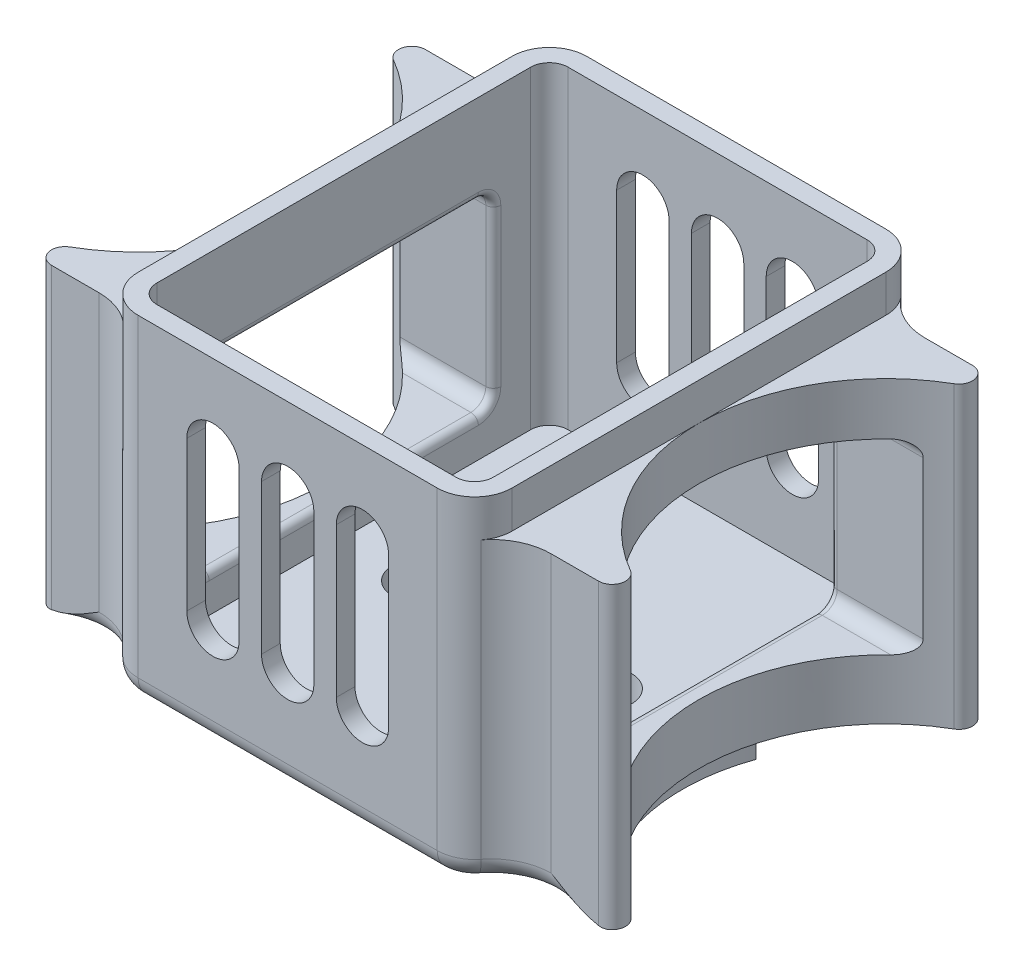
SolidWorks part; units mm, degrees
ref_plane "Alzado" through (0, 0, 0) normal (0, 0, 1) x (1, 0, 0)
ref_plane "Planta" through (0, 0, 0) normal (0, 1, 0) x (1, 0, 0)
ref_plane "Vista lateral" through (0, 0, 0) normal (1, 0, 0) x (0, 0, -1)
sketch "Croquis1" plane through (0, 0, 0) normal (0, 1, 0) x (1, 0, 0)
  line L0 (-25, 0) -> (-50, 0) construction
  line L1 (20, -30) -> (-20, -30)
  line L2 (25, -25) -> (25, 25)
  line L3 (20, 30) -> (-20, 30)
  line L4 (-25, -25) -> (-25, 25)
  line L5 (25, -30) -> (-25, 30) construction
  line L6 (25, 30) -> (-25, -30) construction
  line L7 (-50, 25) -> (-25, 25)
  line L8 (-50, -25) -> (-25, -25)
  line L9 (25, 25) -> (50, 25)
  line L10 (25, -25) -> (50, -25)
  arc A0 (20, -30) -> (25, -25) centre (20, -25) ccw
  arc A1 (-25, -25) -> (-20, -30) centre (-20, -25) ccw
  arc A2 (25, 25) -> (20, 30) centre (20, 25) ccw
  arc A3 (-20, 30) -> (-25, 25) centre (-20, 25) ccw
  arc A4 (-50, -25) -> (-50, 25) centre (-50, 0) ccw
  arc A5 (50, 25) -> (50, -25) centre (50, 0) ccw
  point P0 (0, 0)
  dimension "D3" = 5
  dimension "D4" = 5
  dimension "D5" = 5
  dimension "D6" = 5
  dimension "D8" = 25
  dimension "D1" = 50
  dimension "D2" = 60
  dimension "D7" = 25
extrude "Saliente-Extruir1" add sketch "Croquis1" along normal blind 45 contours L3 A3 L4 A1 L1 A0 L2 A2 | A4 L4 L7 | A4 L8 L4 | A5 L2 L10 | A5 L9 L2
sketch "Croquis2" plane through (0, 45, 0) normal (0, 1, 0) x (1, 0, 0)
  line L0 (-25, 25) -> (-25, -25)
  line L1 (25, 25) -> (25, -25)
  line L2 (20, 27.5) -> (-20, 27.5)
  line L3 (-22.5, 25) -> (-22.5, -25)
  line L4 (-20, -27.5) -> (20, -27.5)
  line L5 (22.5, 25) -> (22.5, -25)
  line L6 (20, 30) -> (-20, 30)
  line L7 (-25, 25) -> (-50, 25)
  line L8 (-50, -25) -> (-25, -25)
  line L9 (-20, -30) -> (20, -30)
  line L10 (25, -25) -> (50, -25)
  line L11 (50, 25) -> (25, 25)
  line L12 (20, 30) -> (-20, 30)
  line L15 (-20, -30) -> (20, -30)
  arc A0 (-20, 27.5) -> (-22.5, 25) centre (-20, 25) ccw
  arc A1 (-22.5, -25) -> (-20, -27.5) centre (-20, -25) ccw
  arc A2 (20, -27.5) -> (22.5, -25) centre (20, -25) ccw
  arc A3 (22.5, 25) -> (20, 27.5) centre (20, 25) ccw
  arc A6 (-20, 30) -> (-25, 25) centre (-20, 25) ccw
  arc A7 (-50, -25) -> (-50, 25) centre (-50, 0) ccw
  arc A8 (-25, -25) -> (-20, -30) centre (-20, -25) ccw
  arc A9 (20, -30) -> (25, -25) centre (20, -25) ccw
  arc A10 (50, 25) -> (50, -25) centre (50, 0) ccw
  arc A11 (25, 25) -> (20, 30) centre (20, 25) ccw
  arc A12 (-20, 30) -> (-25, 25) centre (-20, 25) ccw
  arc A14 (-25, -25) -> (-20, -30) centre (-20, -25) ccw
  arc A15 (20, -30) -> (25, -25) centre (20, -25) ccw
  arc A17 (25, 25) -> (20, 30) centre (20, 25) ccw
  dimension "D1" = 0
  dimension "D2" = 2.5
extrude "Cortar-Extruir1" cut sketch "Croquis2" against normal blind 42 contours L5 A3 L2 A0 L3 A1 L4 A2
sketch "Croquis3" plane through (22.5, 0, 0) normal (-1, 0, 0) x (0, 0, 1)
  line L0 (-25, 43.1) -> (25, 43.1)
  line L1 (-25, 41.6) -> (25, 41.6)
  line L2 (-25, 24) -> (25, 24) construction
  line L3 (-25, 4.9) -> (25, 4.9)
  line L4 (25, 45) -> (-25, 45)
  line L5 (-25, 45) -> (-25, 3)
  line L6 (-25, 3) -> (25, 3)
  line L7 (25, 3) -> (25, 45)
  line L8 (25, 45) -> (-25, 45)
  line L9 (-25, 45) -> (-25, 3)
  line L10 (-25, 3) -> (25, 3)
  line L11 (25, 3) -> (25, 45)
  line L12 (-25, 6.4) -> (25, 6.4)
  dimension "D2" = 1.9
  dimension "D3" = 1.5
  dimension "D1" = 0
sketch "Croquis5" plane through (0, 45, 0) normal (0, 1, 0) x (1, 0, 0)
  line L0 (-25, 25) -> (-25, -25)
  line L1 (25, 25) -> (25, -25)
  line L6 (20, 30) -> (-20, 30)
  line L7 (-25, 25) -> (-50, 25)
  line L8 (-50, -25) -> (-25, -25)
  line L9 (-20, -30) -> (20, -30)
  line L10 (25, -25) -> (50, -25)
  line L11 (50, 25) -> (25, 25)
  line L13 (-25, 25) -> (-50, 25)
  line L14 (-50, -25) -> (-25, -25)
  line L16 (25, -25) -> (50, -25)
  line L17 (50, 25) -> (25, 25)
  arc A8 (-20, 30) -> (-25, 25) centre (-20, 25) ccw
  arc A9 (-50, -25) -> (-50, 25) centre (-50, 0) ccw
  arc A10 (-25, -25) -> (-20, -30) centre (-20, -25) ccw
  arc A11 (20, -30) -> (25, -25) centre (20, -25) ccw
  arc A12 (50, 25) -> (50, -25) centre (50, 0) ccw
  arc A13 (25, 25) -> (20, 30) centre (20, 25) ccw
  arc A15 (-50, -25) -> (-50, 25) centre (-50, 0) ccw
  arc A18 (50, 25) -> (50, -25) centre (50, 0) ccw
  line M15 (-25, 25) -> (-50, 25)
  arc M16 (-50, 25) -> (-50, -25) centre (-50, 0) cw
  line M17 (-50, -25) -> (-25, -25)
  line M21 (25, -25) -> (50, -25)
  arc M22 (50, -25) -> (50, 25) centre (50, 0) cw
  line M23 (50, 25) -> (25, 25)
  dimension "D1" = 0
extrude "Cortar-Extruir2" cut sketch "Croquis5" against normal blind 5 contours L0 M15 M16 | L0 M16 M17 | L1 M23 M22 | L1 M22 M21
sketch "Croquis6" plane through (0, 0, 0) normal (0, -1, 0) x (1, 0, 0)
  line L0 (0, 0) -> (0, 15.1) construction
  line L1 (15, 15.1) -> (-15, 15.1)
  line L2 (0, 15.1) -> (0, 17.1) construction
  line L3 (15, 17.1) -> (-15, 17.1)
  line L4 (-15, 17.1) -> (-15, 15.1)
  line L5 (15, 17.1) -> (15, 15.1)
  line L6 (0, 0) -> (25, 0) construction
  line L7 (15, -17.1) -> (15, -15.1)
  line L9 (15, -15.1) -> (-15, -15.1)
  line L10 (-15, -17.1) -> (-15, -15.1)
  line L18 (15, -17.1) -> (-15, -17.1)
  arc A0 (50, 25) -> (50, -25) centre (50, 0) ccw construction
  point P6 (0, 17.1)
  point P19 (0, 15.1)
  dimension "D2" = 15.1
  dimension "D1" = 2
  dimension "D3" = 30
extrude "Saliente-Extruir3" add sketch "Croquis6" along normal blind 5
sketch "Croquis8" plane through (0, 0, 0) normal (0, -1, 0) x (1, 0, 0)
  line L1 (24.25, 8.375) -> (-24.25, 8.375)
  line L3 (24.75, 0) -> (-24.75, 0) construction
  line L4 (24.25, -8.375) -> (-24.25, -8.375)
  arc A1 (-24.25, -8.375) -> (-24.25, 8.375) centre (-47.8055, 0) ccw
  arc A3 (24.25, 8.375) -> (24.25, -8.375) centre (47.8055, 0) ccw
  point P7 (0, 8.375)
  dimension "D2" = 48.5
  dimension "D3" = 25
  dimension "D1" = 16.75
extrude "Saliente-Extruir4" add sketch "Croquis8" along normal blind 3.5
sketch "Croquis9" plane through (0, -3.5, 0) normal (0, -1, 0) x (1, 0, 0)
  line L0 (-22.8055, 0) -> (22.8055, 0) construction
  line L1 (0, 0) -> (0, 8.375) construction
  line L2 (-24.25, -8.375) -> (24.25, -8.375)
  line L3 (24.25, 8.375) -> (-24.25, 8.375)
  line L4 (-24.25, -8.375) -> (24.25, -8.375) construction
  line L5 (24.25, 8.375) -> (-24.25, 8.375) construction
  circle A0 centre (-12.5, 0) radius 1.55
  circle A1 centre (12.5, 0) radius 1.55
  arc A2 (-24.25, -8.375) -> (-24.25, 8.375) centre (-47.8055, 0) ccw
  arc A3 (24.25, 8.375) -> (24.25, -8.375) centre (47.8055, 0) ccw
  arc A4 (-24.25, -8.375) -> (-24.25, 8.375) centre (-47.8055, 0) ccw construction
  arc A5 (24.25, 8.375) -> (24.25, -8.375) centre (47.8055, 0) ccw construction
  point P8 (-12.5, 0)
  dimension "D3" = 3.1
  dimension "D2" = 12.5
  dimension "D1" = 0
sketch "Croquis12" plane through (0, 0, 0) normal (1, 0, 0) x (0, 0, -1)
  line L1 (-18, 8) -> (18, 8)
  line L2 (-20, 10) -> (-20, 31)
  line L3 (-18, 33) -> (18, 33)
  line L4 (20, 10) -> (20, 31)
  arc A0 (18, 8) -> (20, 10) centre (18, 10) ccw
  arc A1 (18, 33) -> (20, 31) centre (18, 31) cw
  arc A2 (-18, 8) -> (-20, 10) centre (-18, 10) cw
  arc A3 (-20, 31) -> (-18, 33) centre (-18, 31) cw
  point P4 (0, 8)
  point P8 (20, 8)
  point P11 (20, 33)
  point P16 (-20, 33)
  dimension "D4" = 2
  dimension "D1" = 8
  dimension "D2" = 40
  dimension "D3" = 25
extrude "Cortar-Extruir5" cut sketch "Croquis12" against normal through all both and the other way through all
fillet "Redondeo1" radius 1.8 4 edges at (50, 20, -25) (50, 20, 25) (-50, 20, 25) (-50, 20, -25)
fillet "Redondeo5" radius 8 4 edges at (25, 20, -25) (-25, 20, -25) (25, 20, 25) (-25, 20, 25)
fillet "Redondeo6" radius 8 2 edges at (0, 0, -17.1) (0, 0, 17.1)
fillet "Redondeo7" radius 3 6 edges at (26.7387, 0, 25.8103) (-26.7387, 0, 25.8103) (26.7387, 0, -25.8103) (-26.7387, 0, -25.8103) (0, 0, -30) (0, 0, 30)
fillet "Redondeo8" radius 3 2 edges at (0, -5, -17.1) (0, -5, 17.1)
sketch "Croquis13" plane through (0, 0, -27.5) normal (0, 0, 1) x (1, 0, 0)
  line L0 (-17, 42) -> (-17, 6) construction
  line L1 (-17, 6) -> (17, 6) construction
  line L2 (17, 6) -> (17, 42) construction
  line L3 (17, 42) -> (-17, 42) construction
  line L4 (-20, 45) -> (-20, 3)
  line L5 (-20, 3) -> (20, 3)
  line L6 (20, 3) -> (20, 45)
  line L7 (20, 45) -> (-20, 45)
  line L8 (-20, 45) -> (-20, 3) construction
  line L9 (-20, 3) -> (20, 3) construction
  line L10 (20, 3) -> (20, 45) construction
  line L11 (20, 45) -> (-20, 45) construction
  line L12 (-10, 34) -> (-10, 14) construction
  line L13 (-6.5, 34) -> (-6.5, 14)
  line L14 (-13.5, 34) -> (-13.5, 14)
  line L15 (0, 34) -> (0, 14) construction
  line L16 (3.5, 34) -> (3.5, 14)
  line L17 (-3.5, 34) -> (-3.5, 14)
  line L18 (10, 34) -> (10, 14) construction
  line L19 (13.5, 34) -> (13.5, 14)
  line L20 (6.5, 34) -> (6.5, 14)
  arc A0 (-6.5, 34) -> (-13.5, 34) centre (-10, 34) ccw
  arc A1 (-13.5, 14) -> (-6.5, 14) centre (-10, 14) ccw
  arc A2 (3.5, 34) -> (-3.5, 34) centre (0, 34) ccw
  arc A3 (-3.5, 14) -> (3.5, 14) centre (0, 14) ccw
  arc A4 (13.5, 34) -> (6.5, 34) centre (10, 34) ccw
  arc A5 (6.5, 14) -> (13.5, 14) centre (10, 14) ccw
  point P10 (-10, 24)
  point P17 (0, 24)
  point P22 (10, 24)
  dimension "D6" = 3.5
  dimension "D3" = 10
  dimension "D4" = 10
  dimension "D5" = 18
  dimension "D7" = 20
  dimension "D1" = 0
  dimension "D2" = 3
extrude "Cortar-Extruir6" cut sketch "Croquis13" against normal through all both and the other way through all
extrude "Cortar-Extruir7" cut sketch "Croquis9" against normal blind 10 and the other way through all
fillet "Redondeo9" radius 1 16 edges at (-22.5, 32.4142, 19.4142) (-22.5, 20.5, 20) (-22.5, 8.5858, 19.4142) (-22.5, 8, 0) (-22.5, 8.5858, -19.4142) (-22.5, 20.5, -20) (-22.5, 32.4142, -19.4142) (22.5, 32.4142, 19.4142) (22.5, 20.5, 20) (22.5, 8.5858, 19.4142) (22.5, 8, 0) (22.5, 8.5858, -19.4142) (22.5, 20.5, -20) (22.5, 32.4142, -19.4142) (-22.5, 33, 0) (22.5, 33, 0)
sketch "Croquis14" plane through (0, 3, 0) normal (0, 1, 0) x (1, 0, 0)
  circle A0 centre (-12.5, 0) radius 3.5
  circle A1 centre (12.5, 0) radius 3.5
  dimension "D1" = 7
extrude "Cortar-Extruir8" cut sketch "Croquis14" against normal blind 4
